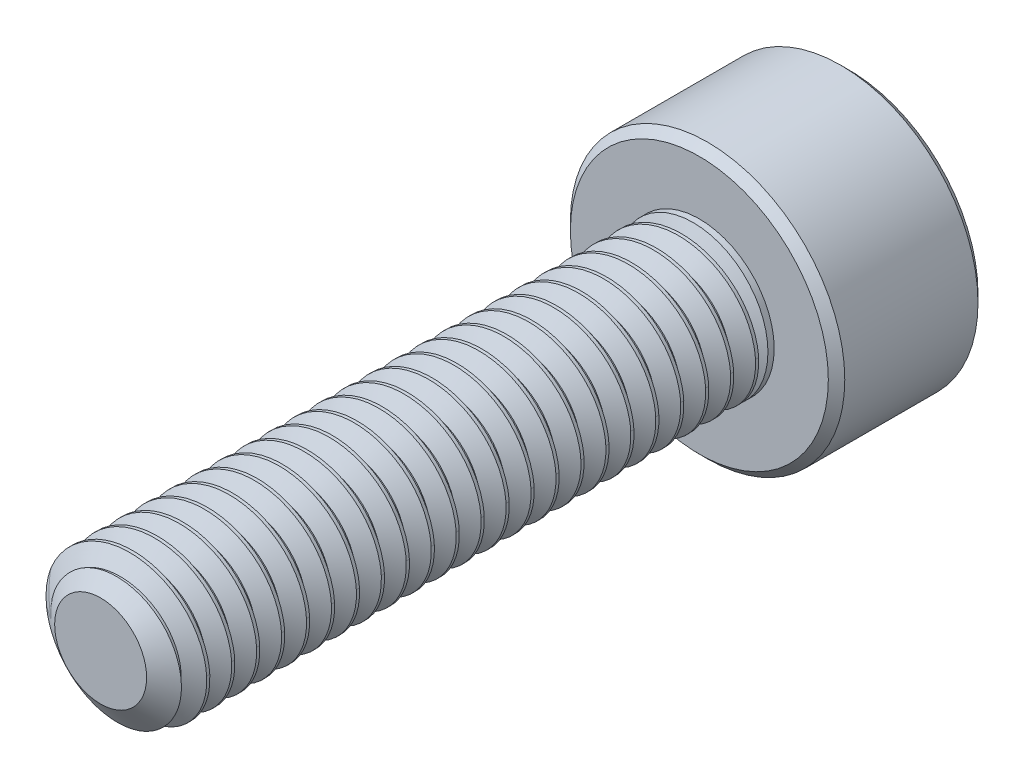
SolidWorks part; units mm, degrees
ref_plane "Front Plane" through (0, 0, 0) normal (0, 0, 1) x (1, 0, 0)
ref_plane "Top Plane" through (0, 0, 0) normal (0, 1, 0) x (1, 0, 0)
ref_plane "Right Plane" through (0, 0, 0) normal (1, 0, 0) x (0, 0, -1)
sketch "Sketch1" plane through (0, 0, 0) normal (0, 0, 1) x (1, 0, 0)
  circle A0 centre (0, 0) radius 1.5
  dimension "OD" = 3
extrude "Extrude1" add sketch "Sketch1" against normal blind 12
sketch "Sketch2" plane through (0, 0, 0) normal (0, 0, 1) x (1, 0, 0)
  circle A0 centre (0, 0) radius 1.5 construction
  circle A1 centre (0, 0) radius 1.5
curve "Helix/Spiral1" pitch 0.5 height 12.5 radius 1.5 centre (0, 0, 0) axis (0, 0, -1) start towards (0, 1, 0) parameters "pitch"=0.5
sketch "Sketch3" plane through (0, 0, 0) normal (1, 0, 0) x (0, 0, -1)
  line L0 (-0.4375, 1.5) -> (-0.25, 1.1752)
  line L1 (-0.25, 1.1752) -> (-0.1875, 1.1752)
  line L2 (-0.1875, 1.1752) -> (0, 1.5)
  line L3 (-0.4375, 1.5) -> (0, 1.5)
  line L4 (-0.2187, 1.5) -> (-0.2187, 1.1752) construction
  line L5 (-0.3437, 1.3376) -> (-0.0937, 1.3376) construction
  line L6 (0, 1.5) -> (0, -1.5) construction
  line L7 (0, -1.5) -> (12, -1.5) construction
  point P11 (2.25, -1.5)
  dimension "D1" = 0.0625
  dimension "D2" = 0.25
  dimension "D3" = 60
  dimension "D4" = 2.25
sweep "Cut-Sweep1" cut profiles "Sketch3" path "Helix/Spiral1" align with end faces yes
sketch "Sketch4" plane through (0, 0, 0) normal (1, 0, 0) x (0, 0, -1)
  line L0 (0.4053, 1.5) -> (0, 0.9212)
  line L1 (0, 0.9212) -> (0, 1.5)
  line L2 (0.4053, 1.5) -> (0, 1.5)
  line L3 (-0.4375, 1.5) -> (0, 1.5) construction
  line L4 (0, 0) -> (7.0209, 0) construction
  dimension "D1" = 55
  dimension "D2" = 0.254
revolve "Cut-Revolve1" cut sketch "Sketch4" angle 360 about L4
sketch "Sketch5" plane through (0, 0, 0) normal (1, 0, 0) x (0, 0, -1)
  line L0 (12, -1.1822) -> (12, 1.0703) construction
  line L1 (12, 1.5) -> (0.1203, 1.5)
  line L2 (12, 1.5) -> (12, 0)
  line L3 (12, 0) -> (0.0001, 0)
  line L4 (0.0001, 1.1698) -> (0.0001, 0)
  line L5 (0.1203, 1.5) -> (0.0001, 1.1698)
  line L6 (0, 0) -> (9.9695, 0) construction
  point P3 (0.0001, 1.5)
  point P10 (0.0001, 1.5)
  dimension "D1" = 0.3302
  dimension "Thread min" = 0.0001
  dimension "D3" = 20
revolve "partially thread" [suppressed] add sketch "Sketch5" angle 360 about L6
sketch "Sketch6" plane through (0, 0, -12) normal (0, 0, -1) x (-1, 0, 0)
  circle A0 centre (0, 0) radius 2.75
  dimension "head dia" = 5.5
extrude "Extrude2" add sketch "Sketch6" along normal blind 3
sketch "Sketch7" plane through (0, 0, -15) normal (0, 0, -1) x (-1, 0, 0)
  line L1 (0, 1.4434) -> (-1.25, 0.7217)
  line L2 (-1.25, 0.7217) -> (-1.25, -0.7217)
  line L3 (-1.25, -0.7217) -> (0, -1.4434)
  line L4 (0, -1.4434) -> (1.25, -0.7217)
  line L5 (1.25, -0.7217) -> (1.25, 0.7217)
  line L6 (1.25, 0.7217) -> (0, 1.4434)
  circle A0 centre (0, 0) radius 1.25 construction
  dimension "hex dia" = 2.5
extrude "Cut-Extrude1" cut sketch "Sketch7" against normal blind 1.875
sketch "Sketch8" plane through (0, 0, -15) normal (0, 0, -1) x (-1, 0, 0)
  circle A0 centre (0, 0) radius 1.4434
extrude "Cut-Extrude2" cut sketch "Sketch8" against normal through all draft 45
chamfer "Chamfer1" distance 0.165 angle 45 2 edges at (-2.75, 0, -15) (-2.75, 0, -12)
sketch "Sketch9" plane through (0, 0, 0) normal (1, 0, 0) x (0, 0, -1)
  line L0 (0, 1.5) -> (0, -1.5) construction
  line L1 (2.75, 1.5) -> (2.75, -1.5) construction
  dimension "D1" = 2.75
sketch "Sketch10" plane through (0, 0, 0) normal (1, 0, 0) x (0, 0, -1)
  line L0 (12, 1.5) -> (12, 0)
  line L1 (12, 1.5) -> (11.875, 1.5)
  line L2 (11.875, 1.5) -> (11.2537, 0)
  line L3 (12, 0) -> (11.2537, 0)
  line L4 (12, 2.585) -> (12, -2.585) construction
  dimension "D1" = 22.5
  dimension "D2" = 0.125
revolve "Revolve1" add sketch "Sketch10" angle 360 about L3
equation "\"D3@Helix/Spiral1\" = \"screw length@Extrude1\"+\"pitch@Helix/Spiral1\""
equation "\"D1@Sketch3\" = \"pitch@Helix/Spiral1\"*.125"
equation "\"D2@Sketch3\" = \"pitch@Helix/Spiral1\"*.5"
equation "\"D1@Cut-Extrude1\" = \"hex dia@Sketch7\"*.75"
equation "\"D1@Chamfer1\" = \"head dia@Sketch6\"*.03"
equation "\"D1@Sketch9\" = \"pitch@Helix/Spiral1\"*5.5"
equation "\"D2@Sketch10\" = \"pitch@Helix/Spiral1\"*.25"
equation "\"D4@Sketch3\" = \"pitch@Helix/Spiral1\"*4.50"
